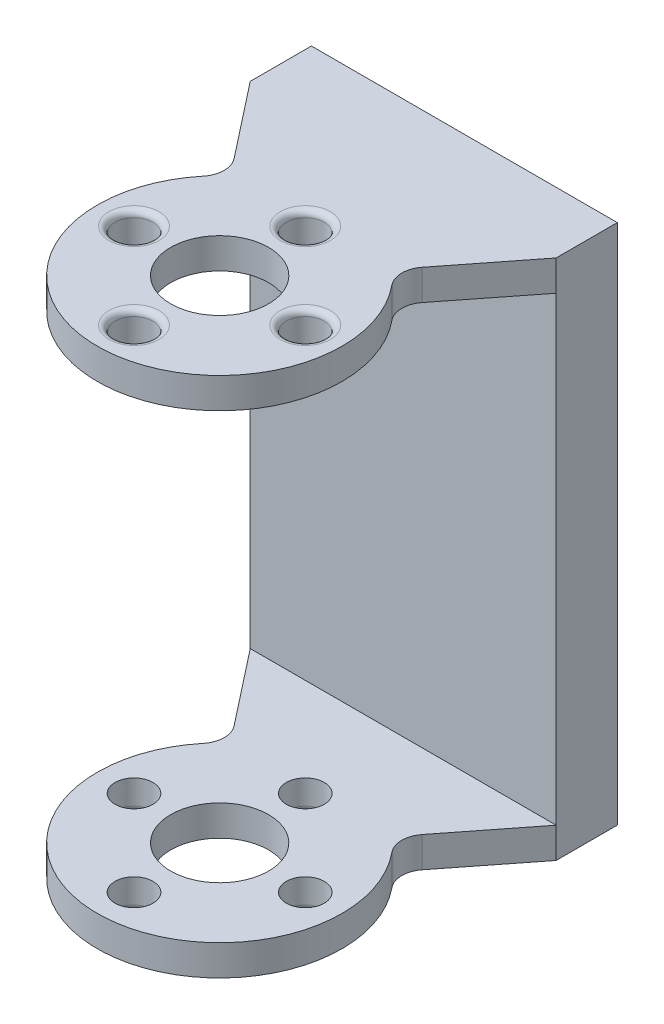
SolidWorks part; units mm, degrees
ref_plane "Front Plane" through (0, 0, 0) normal (0, 0, 1) x (1, 0, 0)
ref_plane "Top Plane" through (0, 0, 0) normal (0, 1, 0) x (1, 0, 0)
ref_plane "Right Plane" through (0, 0, 0) normal (1, 0, 0) x (0, 0, -1)
sketch "Sketch1" plane through (0, 0, 0) normal (0, 1, 0) x (1, 0, 0)
  line L2 (-12.5, 15) -> (-12.5, 20)
  line L3 (-12.5, 20) -> (12.5, 20)
  line L4 (12.5, 15) -> (12.5, 20)
  line L5 (-12.5, 15) -> (-6.6144, 7.5)
  line L6 (6.6144, 7.5) -> (12.5, 15)
  circle A3 centre (0, 0) radius 4
  arc A4 (-6.6144, 7.5) -> (6.6144, 7.5) centre (0, 0) ccw
  point P12 (-12.5, 0)
  point P13 (0, 20)
  dimension "D3" = 0
  dimension "D4" = 20
  dimension "D6" = 8
  dimension "D2" = 10
  dimension "D1" = 25
  dimension "D5" = 5
  dimension "D7" = 12.5
extrude "Boss-Extrude1" add sketch "Sketch1" along normal blind 42.65
sketch "Sketch2" plane through (-12.5, 0, 0) normal (-1, 0, 0) x (0, 0, 1)
  line L1 (25, 2.5) -> (-15, 2.5)
  line L2 (25, 2.5) -> (25, 40.15)
  line L3 (25, 40.15) -> (-15, 40.15)
  line L4 (-15, 2.5) -> (-15, 40.15)
  line L5 (-20, 42.65) -> (-20, 0) construction
  point P6 (-20, 21.325)
  point P7 (25, 21.325)
  dimension "D1" = 37.65
  dimension "D2" = 5
  dimension "D3" = 45
extrude "Cut-Extrude1" cut sketch "Sketch2" against normal through all
ref_plane "B mid plane" through (0, 21.325, 0) normal (0, -1, 0) x (-1, 0, 0)
sketch "Sketch3" plane through (0, 42.65, 0) normal (0, 1, 0) x (1, 0, 0)
  circle A0 centre (0, 7) radius 1.55
  circle A1 centre (0, 0) radius 4 construction
  dimension "D1" = 3.1
  dimension "D2" = 7
  dimension "D3" = 0
extrude "Cut-Extrude2" cut sketch "Sketch3" against normal through all
ref_axis "Axis1" through (0, 42.65, 0) along (0, -1, 0)
pattern_circular "CirPattern1" count 4 over 360 about axis through (0, 42.65, 0) along (0, -1, 0) of "Cut-Extrude2"
fillet "Fillet1" radius 2 4 edges at (6.6144, 41.4, -7.5) (6.6144, 1.25, -7.5) (-6.6144, 41.4, -7.5) (-6.6144, 1.25, -7.5)
fillet "Fillet2" radius 0.5 8 edges at (5.45, 0, 0) (0, 0, 5.45) (-5.45, 0, 0) (0, 0, -5.45) (-5.45, 42.65, 0) (0, 42.65, 5.45) (5.45, 42.65, 0) (0, 42.65, -5.45)
